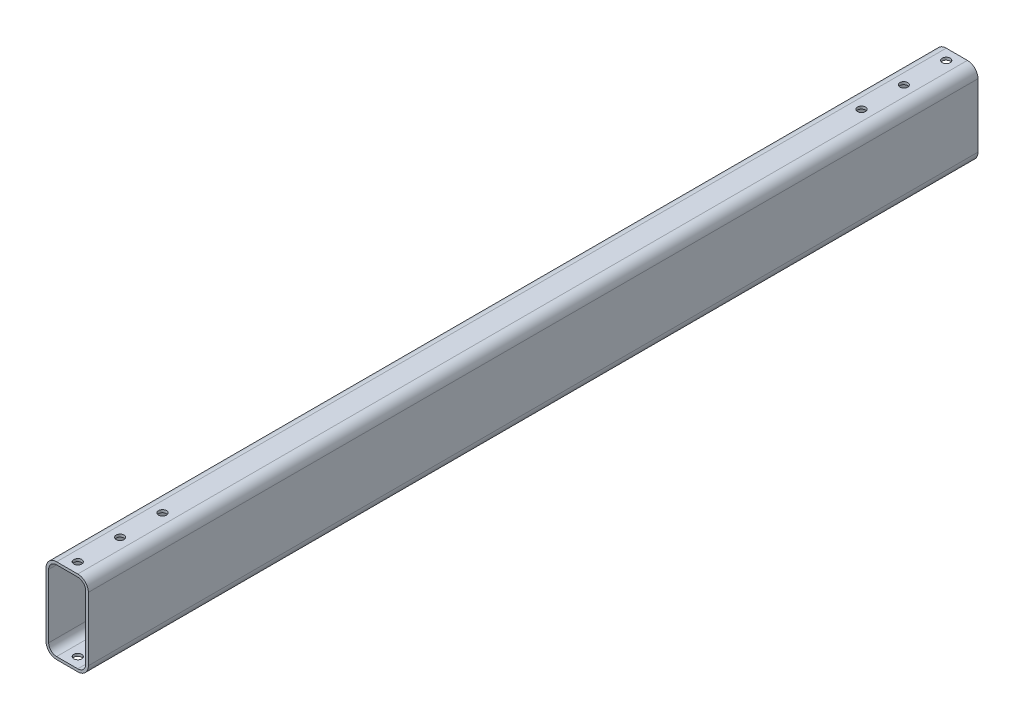
SolidWorks part; units mm, degrees
material "6061-T6 (SS)"
ref_plane "Front Plane" through (0, 0, 0) normal (0, 0, 1) x (1, 0, 0)
ref_plane "Top Plane" through (0, 0, 0) normal (0, 1, 0) x (1, 0, 0)
ref_plane "Right Plane" through (0, 0, 0) normal (1, 0, 0) x (0, 0, -1)
sketch "Sketch1" plane through (0, 0, 0) normal (0, 0, 1) x (1, 0, 0)
  line L1 (-6.35, -25.4) -> (6.35, -25.4)
  line L2 (-12.7, -19.05) -> (-12.7, 19.05)
  line L3 (-6.35, 25.4) -> (6.35, 25.4)
  line L4 (12.7, -19.05) -> (12.7, 19.05)
  line L5 (-12.7, -25.4) -> (12.7, 25.4) construction
  line L6 (-12.7, 25.4) -> (12.7, -25.4) construction
  arc A0 (-12.7, -19.05) -> (-6.35, -25.4) centre (-6.35, -19.05) ccw
  arc A1 (6.35, -25.4) -> (12.7, -19.05) centre (6.35, -19.05) ccw
  arc A2 (6.35, 25.4) -> (12.7, 19.05) centre (6.35, 19.05) cw
  arc A3 (-12.7, 19.05) -> (-6.35, 25.4) centre (-6.35, 19.05) cw
  point P0 (0, 0)
  dimension "D3" = 6.35
  dimension "D1" = 50.8
  dimension "D2" = 25.4
extrude "Extrude-Thin1" add sketch "Sketch1" along normal blind 533.4 thin thin type one direction reverse wall 1.5875
hole_wizard "3/16 (0.1875) Diameter Hole1" positions "3DSketch1" profile "Sketch3" hole size "3/16" standard "ANSI Inch" end condition through all
sketch3d "3DSketch1"
  line L1 (6.35, 25.4, 0) -> (-6.35, 25.4, 0) construction
  line L6 (0, 25.4, 533.4) -> (0, 25.4, 0) construction
  line L7 (6.35, 25.4, 533.4) -> (-6.35, 25.4, 533.4) construction
  point P57 (0, 25.4, 6.35)
  point P59 (0, 25.4, 31.75)
  point P61 (0, 25.4, 57.15)
  point P63 (0, 25.4, 501.65)
  point P65 (0, 25.4, 476.25)
  point P67 (0, 25.4, 527.05)
  dimension "D1" = 25.4
  dimension "D2" = 25.4
  dimension "D3" = 6.35
  dimension "D4" = 25.4
  dimension "D5" = 25.4
  dimension "D6" = 6.35
sketch "Sketch3" plane through (0, 25.4, 527.05) normal (1, 0, 0) x (0, 0, 1)
  line L0 (0, 0) -> (0, 50.8)
  line L1 (0, 50.8) -> (2.3812, 50.8)
  line L2 (2.3812, 50.8) -> (2.3812, 0)
  line L5 (2.3812, 0) -> (0, 0)
  line L11 (0, -6.35) -> (0, 107.95) construction
  dimension "Thru Hole Dia." = 4.7625
  dimension "Thru Hole Depth" = 50.8
hole_wizard "3/16 (0.195) Diameter Hole1" positions "Sketch4" profile "Sketch5" hole size "3/16" standard "ANSI Inch" end condition up to next
sketch "Sketch4" plane through (0, -25.4, 0) normal (0, -1, 0) x (-1, 0, 0)
  point P3 (3.175, -121.1947)
  point P6 (-3.175, -146.5947)
  point P9 (3.175, -171.9947)
  point P12 (-3.175, -197.3947)
  point P15 (-3.175, -349.7947)
  point P18 (3.175, -375.1947)
  point P21 (-3.175, -400.5947)
  point P24 (3.175, -425.9947)
sketch "Sketch5" plane through (-3.175, -25.4, 121.1947) normal (1, 0, 0) x (0, 0, -1)
  line L0 (0, 0) -> (0, 1.5875)
  line L1 (0, 1.5875) -> (2.4765, 1.5875)
  line L2 (2.4765, 1.5875) -> (2.4765, 0)
  line L5 (2.4765, 0) -> (0, 0)
  line L11 (0, -6.35) -> (0, 107.95) construction
  dimension "Thru Hole Dia." = 4.953
  dimension "Thru Hole Depth" = 1.5875
